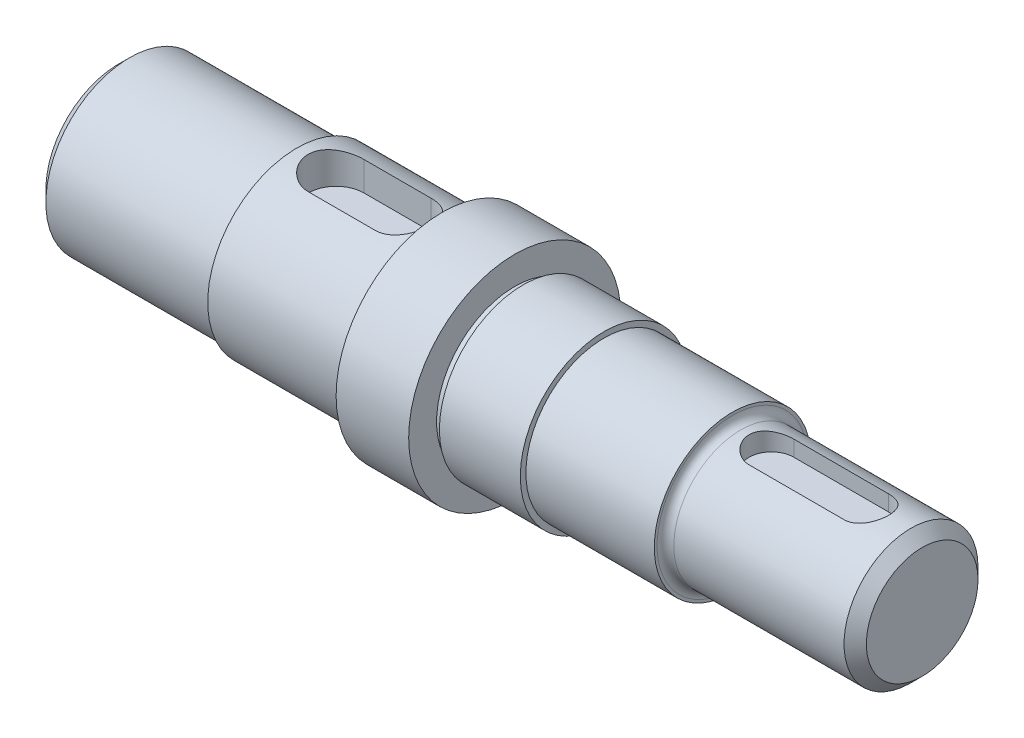
SolidWorks part; units mm, degrees
material "铸造碳钢"
ref_plane "前视基准面" through (0, 0, 0) normal (0, 0, 1) x (1, 0, 0)
ref_plane "上视基准面" through (0, 0, 0) normal (0, 1, 0) x (1, 0, 0)
ref_plane "右视基准面" through (0, 0, 0) normal (1, 0, 0) x (0, 0, -1)
ref_axis "基准轴1" through (88.99, 0, 0) along (-1, 0, 0)
sketch "草图1" plane through (0, 0, 0) normal (1, 0, 0) x (0, 0, -1)
  circle A0 centre (0, 0) radius 15
extrude "凸台-拉伸1" add sketch "草图1" along normal blind 32
chamfer "倒角1" distance 2 angle 45 1 edges at (0, 0, -15)
cosmetic thread "装饰螺纹线1" parameters "D2"=26.211
sketch "草图2" plane through (32, 0, 0) normal (1, 0, 0) x (0, 0, -1)
  circle A0 centre (0, 0) radius 16
extrude "凸台-拉伸2" add sketch "草图2" along normal blind 26
sketch "草图3" plane through (58, 0, 0) normal (1, 0, 0) x (0, 0, -1)
  circle A0 centre (0, 0) radius 19
extrude "凸台-拉伸3" add sketch "草图3" along normal blind 13
sketch "草图4" plane through (71, 0, 0) normal (1, 0, 0) x (0, 0, -1)
  circle A0 centre (0, 0) radius 14
extrude "凸台-拉伸4" add sketch "草图4" along normal blind 1.5
sketch "草图5" plane through (72.5, 0, 0) normal (1, 0, 0) x (0, 0, -1)
  circle A0 centre (0, 0) radius 15
extrude "凸台-拉伸5" add sketch "草图5" along normal blind 14.5
sketch "草图6" plane through (87, 0, 0) normal (1, 0, 0) x (0, 0, -1)
  circle A0 centre (0, 0) radius 14
extrude "凸台-拉伸6" add sketch "草图6" along normal blind 23
sketch "草图7" plane through (110, 0, 0) normal (1, 0, 0) x (0, 0, -1)
  circle A0 centre (0, 0) radius 12
extrude "凸台-拉伸7" add sketch "草图7" along normal blind 34
fillet "圆角1" radius 1.5 1 edges at (110, 0, -12)
chamfer "倒角2" distance 2 angle 45 1 edges at (144, 0, -12)
sketch "草图8" plane through (0, 0, 0) normal (0, 1, 0) x (1, 0, 0)
  line L0 (39, 0) -> (51, 0) construction
  line L1 (39, 5) -> (51, 5)
  line L2 (39, -5) -> (51, -5)
  line L3 (58, 19) -> (58, -19) construction
  arc A0 (39, 5) -> (39, -5) centre (39, 0) ccw
  arc A1 (51, -5) -> (51, 5) centre (51, 0) ccw
  point P3 (45, 0)
  point P8 (56, 0)
  dimension "D1" = 5
  dimension "D2" = 12
  dimension "D3" = 2
extrude "切除-拉伸1" cut sketch "草图8" against normal blind 6 from offset 16
sketch "草图9" plane through (0, 0, 0) normal (0, 1, 0) x (1, 0, 0)
  line L0 (117, 0) -> (134, 0) construction
  line L1 (117, 4) -> (134, 4)
  line L2 (117, -4) -> (134, -4)
  line L3 (110, -14) -> (110, 14) construction
  arc A0 (117, 4) -> (117, -4) centre (117, 0) ccw
  arc A1 (134, -4) -> (134, 4) centre (134, 0) ccw
  point P3 (125.5, 0)
  point P10 (113, 0)
  dimension "D2" = 4
  dimension "D1" = 17
  dimension "D3" = 3
extrude "切除-拉伸2" cut sketch "草图9" against normal blind 3.5 from offset 12
